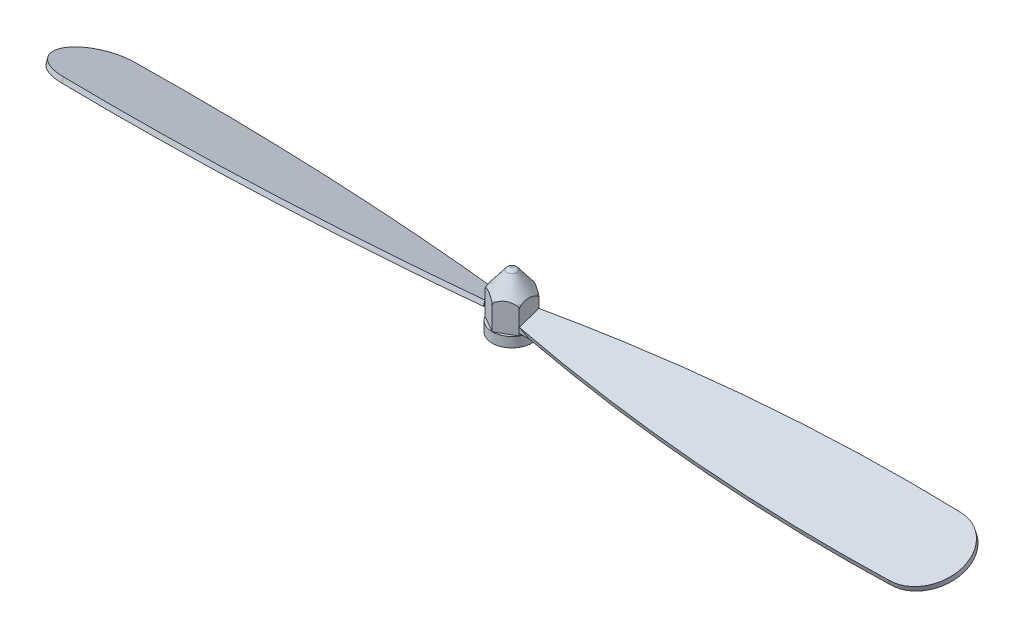
SolidWorks part; units mm, degrees
ref_plane "Front Plane" through (0, 0, 0) normal (0, 0, 1) x (1, 0, 0)
ref_plane "Top Plane" through (0, 0, 0) normal (0, 1, 0) x (1, 0, 0)
ref_plane "Right Plane" through (0, 0, 0) normal (1, 0, 0) x (0, 0, -1)
sketch "Sketch1" plane through (0, 0, 0) normal (0, 0, 1) x (1, 0, 0)
  line L0 (0, 3) -> (0, 5.6424)
  line L1 (0, 0) -> (2, 0)
  line L2 (0, 0) -> (0, 3)
  line L4 (2, 0) -> (2, 3)
  line L7 (0, 5.6424) -> (0.104, 5.6424)
  line L8 (0.5001, 5.4474) -> (1.8961, 3.6349)
  line L9 (2, 3.3298) -> (2, 3)
  arc A0 (1.8961, 3.6349) -> (2, 3.3298) centre (1.5, 3.3298) cw
  arc A1 (0.104, 5.6424) -> (0.5001, 5.4474) centre (0.104, 5.1424) cw
  point P4 (1.125, 1.5)
  point P11 (2, 3.5)
  point P14 (0.35, 5.6424)
  dimension "D6" = 0.5
  dimension "D1" = 2
  dimension "D2" = 3
  dimension "D3" = 0.5
  dimension "D4" = 2.7041
  dimension "D5" = 0.35
revolve "Revolve1" add sketch "Sketch1" angle 360 about L2
sketch "Sketch2" plane through (0, 0, 0) normal (0, -1, 0) x (1, 0, 0)
  line L1 (0, -2) -> (1.7321, -1)
  line L2 (1.7321, -1) -> (1.7321, 1)
  line L3 (1.7321, 1) -> (0, 2)
  line L4 (0, 2) -> (-1.7321, 1)
  line L5 (-1.7321, 1) -> (-1.7321, -1)
  line L6 (-1.7321, -1) -> (0, -2)
  circle A1 centre (0, 0) radius 2
  circle M2 centre (0, 0) radius 2
extrude "Cut-Extrude1" cut sketch "Sketch2" against normal through all contours L5 M2 | L4 M2 | L3 M2 | L2 M2 | L1 M2 | L6 M2 region at (-0.9199, 0, -1.5934) region at (0.9199, 0, -1.5934) region at (1.8399, 0, 0) region at (-1.8399, 0, 0) region at (0.9199, 0, 1.5934) region at (-0.9199, 0, 1.5934)
sketch "Sketch3" plane through (0, 0, 0) normal (0, -1, 0) x (1, 0, 0)
  circle A0 centre (0, 0) radius 1
  dimension "D1" = 2
extrude "Cut-Extrude3" cut sketch "Sketch3" against normal blind 4
sketch "Sketch4" plane through (1.7321, 0, 0) normal (1, 0, 0) x (0, 0, -1)
  line L0 (-1, 1.5) -> (1, 1.5) construction
  line L1 (-1, 1.5) -> (1, 2.1498) construction
  line L2 (0, 0) -> (0, 3.6498) construction
  line L3 (-1, 1.7629) -> (1, 2.4127)
  line L4 (-1, 1.2371) -> (1, 1.887)
  line L7 (1, 0) -> (-1, 0) construction
  line L8 (-1, 3.3298) -> (-1, 0) construction
  line L9 (1, 0) -> (1, 3.3298) construction
  line L10 (-1, 1.7629) -> (-1, 1.2371)
  line L11 (1, 2.4127) -> (1, 1.887)
  point P3 (0, 1.5)
  point P7 (0, 1.8249)
  dimension "D1" = 2
  dimension "D2" = 18
  dimension "D3" = 0.25
  dimension "D4" = 0.25
  dimension "D5" = 1.5
extrude "Boss-Extrude1" add sketch "Sketch4" along normal blind 40
sketch "Sketch5" plane through (0, 0, 0) normal (0, 1, 0) x (1, 0, 0)
  circle A0 centre (0, 0) radius 2
  dimension "D1" = 4
extrude "Boss-Extrude2" add sketch "Sketch5" along normal blind 1
pattern_circular "CirPattern1" count 2 every 180 about axis through (0, 0, 0) along (0, 1, 0) of "Boss-Extrude1"
sketch "Sketch7" plane through (0, 1.8884, -0.6136) normal (0, 0.9511, -0.309) x (1, 0, 0)
  line L0 (-1.7321, 0.4063) -> (-41.7321, 2.3548) construction
  line L1 (-1.7321, -1.6966) -> (-41.7321, -3.6452) construction
  line L2 (-41.7321, -0.6452) -> (-41.7321, 2.3548) construction
  line L3 (-41.7321, -1.6966) -> (-41.7321, 0.4063) construction
  line L4 (-41.7321, -0.6452) -> (-41.7321, -3.6452) construction
  line L5 (-41.7321, -0.6452) -> (-1.7321, -0.6452) construction
  line L6 (-1.7321, -1.6966) -> (-1.7321, 0.4063) construction
  line L7 (-1.7321, 0.4063) -> (-1.7321, -1.6966)
  line L8 (-41.7321, -0.6452) -> (-41.7321, 3.1548) construction
  arc A0 (-41.7321, -3.6452) -> (-41.7321, 2.3548) centre (-42.2653, -0.6452) cw construction
  arc A2 (-41.7321, 3.1548) -> (-41.7321, -4.4452) centre (-41.7321, -0.6452) ccw
  spline S0 degree 2 poles (-41.7321, -3.6452) (-21.5934, -4.1559) (-1.7321, -1.6966) knots 0 0 0 0.839204 0.839204 0.839204 construction
  spline S1 degree 2 poles (-41.7321, 2.3548) (-21.5934, 2.8656) (-1.7321, 0.4063) knots 0 0 0 0.839204 0.839204 0.839204 construction
  spline S2 degree 2 poles (-1.7321, 0.4063) (-21.7037, 3.6421) (-41.7321, 3.1548) knots 0 0 0 0.87036 0.87036 0.87036
  spline S3 degree 2 poles (-1.7321, -1.6966) (-21.7037, -4.9324) (-41.7321, -4.4452) knots 0 0 0 0.87036 0.87036 0.87036
  dimension "D1" = 3.8
  dimension "D2" = 3
extrude "Boss-Extrude5" add sketch "Sketch7" against normal blind 0.5
pattern_circular "CirPattern2" count 2 over 180 about axis through (0, 0, 0) along (0, 1, 0) of "Boss-Extrude5"
